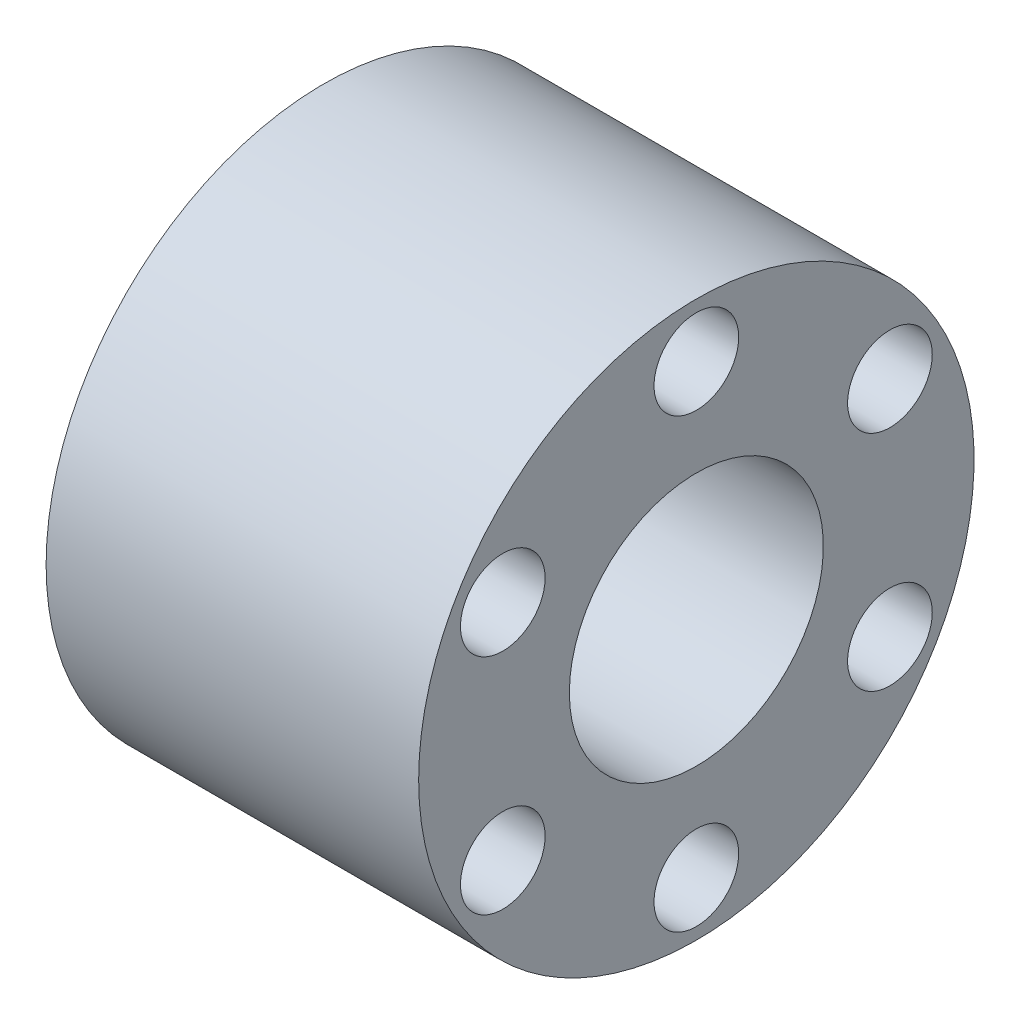
SolidWorks part; units mm, degrees
ref_plane "Front Plane" through (0, 0, 0) normal (0, 0, 1) x (1, 0, 0)
ref_plane "Top Plane" through (0, 0, 0) normal (0, 1, 0) x (1, 0, 0)
ref_plane "Right Plane" through (0, 0, 0) normal (1, 0, 0) x (0, 0, -1)
sketch "Sketch1" plane through (0, 0, 0) normal (1, 0, 0) x (0, 0, -1)
  circle A0 centre (0, 0) radius 4.7625
  circle A1 centre (0, 0) radius 10.414
  dimension "D1" = 9.525
  dimension "D2" = 20.828
extrude "Boss-Extrude1" add sketch "Sketch1" along normal blind 7.62
sketch "Sketch2" plane through (0, 0, 0) normal (-1, 0, 0) x (0, 0, 1)
  circle A0 centre (0, 0) radius 10.414
  circle A1 centre (0, 0) radius 6.35
  dimension "D1" = 12.7
extrude "Boss-Extrude2" add sketch "Sketch2" along normal blind 6.35
sketch "Sketch3" plane through (7.62, 0, 0) normal (1, 0, 0) x (0, 0, -1)
  circle A0 centre (0, 0) radius 8.382 construction
  circle A1 centre (0, 8.382) radius 1.5875
  circle A2 centre (7.259, 4.191) radius 1.5875
  circle A3 centre (7.259, -4.191) radius 1.5875
  circle A4 centre (0, -8.382) radius 1.5875
  circle A5 centre (-7.259, -4.191) radius 1.5875
  circle A6 centre (-7.259, 4.191) radius 1.5875
  point P17 (0, 0)
  dimension "D1" = 16.764
  dimension "D2" = 3.175
  dimension "D3" = 6
extrude "Cut-Extrude1" cut sketch "Sketch3" against normal through all
